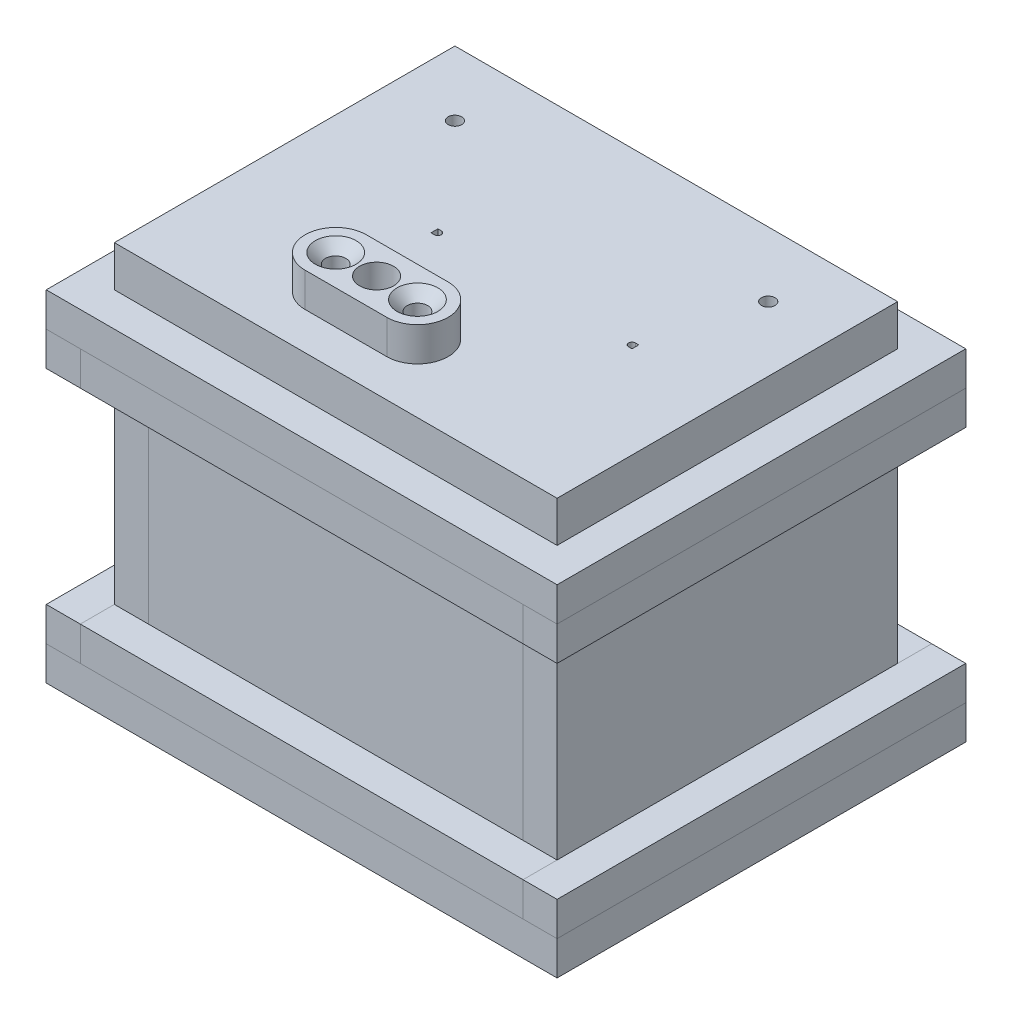
SolidWorks part; units mm, degrees
note: '?' marks a value the reader was unsure of. The reader was unsure of these and kept them because the rebuilt part matched: shared geometry of "Sketch2<6>", "Sketch41<4>", "Sketch41<3>".
ref_plane "Front Plane" through (0, 0, 0) normal (0, 0, 1) x (1, 0, 0)
ref_plane "Top Plane" through (0, 0, 0) normal (0, 1, 0) x (1, 0, 0)
ref_plane "Right Plane" through (0, 0, 0) normal (1, 0, 0) x (0, 0, -1)
sketch "Sketch1" plane through (0, 0, 0) normal (0, 1, 0) x (1, 0, 0)
  line L1 (-36, 0) -> (29, 0)
  line L2 (-36, 0) -> (-36, 50)
  line L3 (-36, 50) -> (29, 50)
  line L4 (29, 0) -> (29, 50)
  dimension "D1" = 50
  dimension "D2" = 36
  dimension "D3" = 29
extrude "Boss-Extrude1" add sketch "Sketch1" along normal blind 5 contours L2 L3 L4 L1
sketch "Sketch2" plane through (0, 5, 0) normal (0, 1, 0) x (1, 0, 0)
  line L0 (-36, 0) -> (29, 0) construction
  line L1 (-36, 50) -> (-31, 50)
  line L2 (-36, 50) -> (-36, 0)
  line L3 (-36, 0) -> (-31, 0)
  line L4 (-31, 50) -> (-31, 0)
  line L6 (29, 50) -> (24, 50)
  line L7 (29, 50) -> (29, 0)
  line L8 (29, 0) -> (24, 0)
  line L9 (24, 50) -> (24, 0)
  line L10 (-31, 50) -> (24, 50)
  line L11 (-31, 50) -> (-31, 45)
  line L12 (-31, 45) -> (24, 45)
  line L13 (24, 50) -> (24, 45)
  line L14 (-31, 0) -> (24, 0)
  line L15 (-31, 0) -> (-31, 5)
  line L16 (-31, 5) -> (24, 5)
  line L17 (24, 0) -> (24, 5)
  point P18 (24, 47.5)
  line M14 (-36, 0) -> (29, 0)
  line M15 (29, 0) -> (29, 50)
  line M16 (29, 50) -> (-36, 50)
  line M17 (-36, 50) -> (-36, 0)
  dimension "D1" = 5
extrude "Boss-Extrude24" add sketch "Sketch2" along normal blind 40 separate body contours L9 M16 M14 M15 | L4 M16 M17 M14 | L14 L17 L16 L15
extrude "Boss-Extrude25" add sketch "Sketch2<6>" along normal up to surface (40 mm away) separate body contours L4 L12 L9 M16 | L16 L4 L9 M14 up to face at (26.5, 45, -25)
sketch "Sketch2<6>" plane through (0, 5, 0) normal (0, 1, 0) x (1, 0, 0) same geometry as "Sketch2"
sketch "Sketch3" plane through (0, 45, 0) normal (0, 1, 0) x (1, 0, 0)
  line L1 (-36, 50) -> (29, 50)
  line L2 (-36, 50) -> (-36, 0)
  line L3 (-36, 0) -> (29, 0)
  line L4 (29, 50) -> (29, 0)
extrude "Boss-Extrude4" add sketch "Sketch3" along normal blind 5 separate body
sketch "Sketch18" plane through (0, 50, 0) normal (0, 1, 0) x (1, 0, 0)
  line L0 (-36, 0) -> (29, 0) construction
  line L1 (-28.5, 42.5) -> (21.5, 42.5)
  line L2 (-28.5, 42.5) -> (-28.5, 7.5)
  line L3 (-28.5, 7.5) -> (21.5, 7.5)
  line L8 (21.5, 42.5) -> (21.5, 7.5)
  line L12 (-31, 45) -> (24, 45) construction
  line L13 (-31, 50) -> (-31, 45) construction
  line L17 (24, 50) -> (24, 0) construction
  dimension "D1" = 2.5
  dimension "D2" = 2.5
  dimension "D3" = 7.5
  dimension "D8" = 2.5
extrude "Cut-Extrude3" cut sketch "Sketch18" against normal through all
sketch "Sketch17" plane through (0, 50, 0) normal (0, 1, 0) x (1, 0, 0)
  line L4 (-36, 50) -> (-36, 0)
  line L5 (-36, 0) -> (29, 0)
  line L6 (29, 0) -> (29, 50)
  line L7 (29, 50) -> (-36, 50)
  line L8 (-36, 50) -> (-36, 0)
  line L9 (-36, 0) -> (29, 0)
  line L10 (29, 0) -> (29, 50)
  line L11 (29, 50) -> (-36, 50)
  dimension "D1" = 0
extrude "Boss-Extrude8" add sketch "Sketch17" along normal blind 6 separate body
ref_plane "Anode" through (-14, 0, 0) normal (1, 0, 0) x (0, 0, -1)
sketch "Sketch6" plane through (-14, 0, 0) normal (1, 0, 0) x (0, 0, -1)
  line L0 (5, 25) -> (45, 25) construction
  line L2 (15.75, 45) -> (15.75, 15.75)
  line L3 (15.75, 15.75) -> (34.25, 15.75)
  line L4 (34.25, 45) -> (34.25, 15.75)
  line L5 (50, 45) -> (0, 45) construction
  line L6 (25, 18.75) -> (25, 31.25) construction
  line L7 (18.75, 31.25) -> (31.25, 31.25)
  line L8 (18.75, 31.25) -> (18.75, 18.75)
  line L9 (18.75, 18.75) -> (31.25, 18.75)
  line L10 (31.25, 31.25) -> (31.25, 18.75)
  line L12 (45, 45) -> (45, 5) construction
  line L16 (34.25, 45) -> (15.75, 45)
  line L17 (5, 45) -> (5, 5) construction
  line L22 (50, 50) -> (0, 50) construction
  line L23 (34.25, 45) -> (15.75, 45)
  line L24 (34.25, 45) -> (34.25, 50)
  line L25 (34.25, 50) -> (15.75, 50)
  line L26 (15.75, 45) -> (15.75, 50)
  point P15 (25, 25)
  dimension "D1" = 12.5
  dimension "D2" = 3
  dimension "D3" = 3
  dimension "D4" = 3
extrude "Boss-Extrude6" add sketch "Sketch6" along normal blind 5 separate body contours L26 L16 L24 L25
ref_plane "Cathode" through (10.5, 0, 0) normal (1, 0, 0) x (0, 0, -1)
sketch "Sketch7" plane through (10.5, 0, 0) normal (1, 0, 0) x (0, 0, -1)
  line L1 (15.75, 50) -> (34.25, 50)
  line L2 (15.75, 50) -> (15.75, 15.75)
  line L3 (15.75, 15.75) -> (34.25, 15.75)
  line L4 (34.25, 50) -> (34.25, 15.75)
extrude "Boss-Extrude7" add sketch "Sketch7" along normal blind 5 separate body
hole_wizard "M3 Clearance Hole1" [suppressed] positions "Sketch12" profile "Sketch10" hole size "M3" standard "ANSI Metric"
sketch "Sketch12" plane through (0, 56, 0) normal (0, 1, 0) x (1, 0, 0)
  line L1 (-36, 50) -> (-36, 0) construction
  line L9 (-31, 47.5) -> (-36, 47.5) construction
  line L16 (24, 47.5) -> (29, 47.5) construction
  line L18 (29, 0) -> (29, 50) construction
  line L19 (24, 25) -> (29, 25) construction
  line L21 (-36, 25) -> (-31, 25) construction
  line L23 (24, 2.5) -> (29, 2.5) construction
  line L26 (-31, 2.5) -> (-36, 2.5) construction
  line L54 (-13.5, 47.5) -> (-33.5, 47.5) construction
  line L66 (24, 50) -> (24, 45) construction
  line L67 (-31, 50) -> (-31, 45) construction
  line L68 (24, 50) -> (24, 0) construction
  line L69 (-31, 50) -> (-31, 0) construction
  line L70 (-13.5, 47.5) -> (6.5, 47.5) construction
  line L71 (6.5, 47.5) -> (26.5, 47.5) construction
  line L73 (6.5, 2.5) -> (26.5, 2.5) construction
  line L74 (-13.5, 2.5) -> (6.5, 2.5) construction
  line L75 (-13.5, 2.5) -> (-33.5, 2.5) construction
  point P47 (-33.5, 47.5)
  point P49 (-33.5, 25)
  point P55 (26.5, 47.5)
  point P57 (26.5, 25)
  point P68 (26.5, 2.5)
  point P71 (-33.5, 2.5)
  point P206 (-13.5, 47.5)
  point P209 (6.5, 47.5)
  point P212 (6.5, 47.5)
  point P218 (6.5, 2.5)
  point P219 (6.5, 2.5)
  point P220 (-13.5, 2.5)
sketch "Sketch10" plane through (-13.5, 56, -2.5) normal (1, 0, 0) x (0, 0, 1)
  line L0 (0, 0) -> (0, 56)
  line L1 (0, 56) -> (1.7, 56)
  line L2 (1.7, 56) -> (1.7, 0)
  line L5 (1.7, 0) -> (0, 0)
  line L11 (0, -6.35) -> (0, 107.95) construction
  dimension "Thru Hole Dia." = 3.4
  dimension "Thru Hole Depth" = 56
hole_wizard "M3x0.5 Tapped Hole1" [suppressed] positions "Sketch14" profile "Sketch15" tap size "M3x0.5" standard "ANSI Metric"
sketch "Sketch14" [suppressed] plane through (0, 50, 0) normal (0, 1, 0) x (1, 0, 0)
  point P0 (-33.5, 47.5)
  point P5 (6.5, 47.5)
  point P8 (26.5, 47.5)
  point P11 (26.5, 25)
  point P14 (26.5, 2.5)
  point P20 (6.5, 2.5)
  point P23 (-33.5, 2.5)
  point P26 (-33.5, 25)
  point P39 (-13.5, 2.5)
  point P42 (-13.5, 47.5)
sketch "Sketch15" plane through (-33.5, 50, -47.5) normal (1, 0, 0) x (0, 0, 1)
  line L0 (0, 0) -> (0, 8.2511)
  line L1 (0, 8.2511) -> (1.25, 7.5)
  line L2 (1.25, 7.5) -> (1.25, 0)
  line L5 (1.25, 0) -> (0, 0)
  line L10 (0, 8.2511) -> (-1.25, 7.5) construction
  line L11 (0, -6.35) -> (0, 107.95) construction
  dimension "Tap Drill Dia." = 2.5
  dimension "Tap Drill Depth" = 7.5
  dimension "Drill Angle" = 118
sketch "Sketch19" plane through (0, 56, 0) normal (0, 1, 0) x (1, 0, 0)
  line L0 (0.75, 25) -> (-13.5, 25) construction
  line L1 (21.5, 7.5) -> (21.5, 42.5) construction
  line L2 (-28.5, 42.5) -> (-28.5, 7.5) construction
  line L3 (-13.5, 25.5) -> (-14, 25.5)
  line L5 (-14, 25.5) -> (-14, 24.5)
  line L6 (-14, 24.5) -> (-13.5, 24.5)
  line L8 (21.5, 42.5) -> (-28.5, 42.5) construction
  line L14 (15, 25) -> (0.75, 25) construction
  line L15 (15.5, 34.25) -> (15.5, 15.75) construction
  line L16 (-26.5, 40.5) -> (19.5, 40.5) construction
  line L17 (-14, 25.5) -> (-13.5, 25.5)
  line L18 (15, 25) -> (15.5, 25) construction
  line L19 (19.5, 40.5) -> (19.5, 42.5) construction
  line L21 (-13.5, 24.5) -> (-14, 24.5)
  line L22 (-13.5, 25.5) -> (-14, 25.5)
  line L23 (-14, 24.5) -> (-13.5, 24.5)
  line L24 (-14, 25.5) -> (-13.5, 25.5)
  line L25 (-28.5, 7.5) -> (21.5, 7.5) construction
  line L26 (-13.5, 24.5) -> (-14, 24.5)
  line L27 (15, 24.5) -> (15.5, 24.5)
  line L28 (15.5, 25.5) -> (15, 25.5)
  line L31 (15.5, 24.5) -> (15, 24.5)
  line L32 (15, 25.5) -> (15.5, 25.5)
  line L33 (15, 24.5) -> (15.5, 24.5)
  line L34 (15.5, 25.5) -> (15, 25.5)
  line L35 (15.5, 24.5) -> (15, 24.5)
  line L36 (15.5, 25.5) -> (15.5, 24.5)
  line L37 (15, 25.5) -> (15.5, 25.5)
  line L39 (-14, 34.25) -> (-14, 15.75) construction
  arc A0 (-13.5, 24.5) -> (-13.5, 25.5) centre (-13.5, 25) ccw
  circle A2 centre (-7.5, 10) radius 2.5
  circle A3 centre (-26.5, 40.5) radius 1
  circle A4 centre (19.5, 40.5) radius 1
  arc A5 (15, 24.5) -> (15, 25.5) centre (15, 25) cw
  dimension "D1" = 1
  dimension "D2" = 5
  dimension "D5" = 2
  dimension "D7" = 2
  dimension "D8" = 2
  dimension "D3" = 2.5
  dimension "D4" = 21
  dimension "D6" = 2
extrude "Cut-Extrude4" cut sketch "Sketch19" against normal offset from surface (30.25 mm away) 10 contours A3 | L6 A0 L3 L5 | A2 | A4 | A5 L27 L36 L28 up to face at (-11.5, 15.75, -25)
sketch "Sketch23" [suppressed] plane through (0, 0, 0) normal (0, 0, 1) x (1, 0, 0)
  line L0 (-14, 50) -> (-14, 15.75) construction
  line L1 (-31, 42) -> (3, 42) construction
  line L2 (3, 25) -> (-31, 25) construction
  line L4 (-31, 45) -> (-31, 5) construction
  line L5 (3, 42) -> (3, 8) construction
  line L6 (-14, 39) -> (-14, 11) construction
  line L7 (-28, 39) -> (0, 39) construction
  line L8 (-28, 39) -> (-28, 11) construction
  line L9 (-28, 11) -> (0, 11) construction
  line L10 (0, 39) -> (0, 11) construction
  line L11 (-31, 8) -> (3, 8) construction
  line L12 (-31, 42) -> (-31, 8) construction
  circle A0 centre (-14, 25) radius 10
  circle A1 centre (-28, 39) radius 1.25
  circle A2 centre (0, 39) radius 1.25
  circle A3 centre (0, 11) radius 1.25
  circle A4 centre (-28, 11) radius 1.25
  circle A5 centre (-31, 42) radius 1.25
  circle A6 centre (3, 42) radius 1.25
  circle A7 centre (3, 8) radius 1.25
  circle A8 centre (-31, 8) radius 1.25
  point P12 (-14, 25)
  dimension "D1" = 20
  dimension "D3" = 2.5
  dimension "D2" = 28
  dimension "D4" = 3
sketch "Sketch24" [suppressed] plane through (-36, 0, -41) normal (1, 0, 0) x (0, 0, -1)
  line L0 (-33, 42) -> (1, 42) construction
  line L1 (-36, 45) -> (-36, 5) construction
  line L2 (4, 25) -> (-36, 25) construction
  line L3 (1, 42) -> (1, 8) construction
  line L4 (-33, 8) -> (1, 8) construction
  line L5 (4, 45) -> (4, 5) construction
  line L6 (-16, 39) -> (-16, 11) construction
  line L7 (-30, 39) -> (-2, 39) construction
  line L8 (-30, 39) -> (-30, 11) construction
  line L9 (-30, 11) -> (-2, 11) construction
  line L10 (-2, 39) -> (-2, 11) construction
  line L11 (-33, 42) -> (-33, 8) construction
  circle A0 centre (-16, 25) radius 10
  circle A1 centre (-30, 39) radius 1.25
  circle A2 centre (-2, 39) radius 1.25
  circle A3 centre (-2, 11) radius 1.25
  circle A4 centre (-30, 11) radius 1.25
  circle A5 centre (1, 42) radius 1.25
  circle A6 centre (-33, 42) radius 1.25
  circle A7 centre (-33, 8) radius 1.25
  circle A8 centre (1, 8) radius 1.25
  point P12 (-16, 25)
  point P23 (-16, 25)
  dimension "D1" = 20
  dimension "D3" = 2.5
  dimension "D2" = 28
  dimension "D4" = 3
ref_plane "Plane1" through (0, 25, 0) normal (0, -1, 0) x (-1, 0, 0)
ref_plane "Plane2" through (0, 0, -25) normal (0, 0, 1) x (1, 0, 0)
ref_plane "Plane3" through (-14, 0, 0) normal (-1, 0, 0) x (0, 0, 1)
ref_axis "Axis1" through (47.9997, 25, -25) along (-1, 0, 0)?
ref_axis "Axis2" through (-14, 25, 7.75) along (0, 0, -1)?
ref_plane "Plane4" through (0, 0, 41.5) normal (0, 0, 1) x (1, 0, 0)
sketch "Sketch31" plane through (0, 56, 0) normal (0, 1, 0) x (1, 0, 0)
  line L0 (-10, 10) -> (-13.5, 10) construction
  line L2 (-7.5, 7.5) -> (-7.5, 12.5) construction
  line L3 (-1.5, 10) -> (-13.5, 10) construction
  line L4 (-1.5, 5.5) -> (-13.5, 5.5)
  line L5 (-1.5, 14.5) -> (-13.5, 14.5)
  circle A1 centre (-7.5, 10) radius 2.5
  circle A2 centre (-7.5, 10) radius 2.5 construction
  circle A3 centre (-13.5, 10) radius 1.5
  circle A4 centre (-1.5, 10) radius 1.5
  arc A5 (-1.5, 5.5) -> (-1.5, 14.5) centre (-1.5, 10) ccw
  arc A6 (-13.5, 14.5) -> (-13.5, 5.5) centre (-13.5, 10) ccw
  point P14 (-7.5, 10)
  dimension "D1" = 9
  dimension "D2" = 3
  dimension "D3" = 12
extrude "Boss-Extrude18" add sketch "Sketch31" along normal blind 5 separate body
chamfer "Chamfer1" distance 2 angle 45 1 edges at (-7.5, 56, -7.5)
chamfer "Chamfer2" distance 1.5 angle 45 2 edges at (-1.5, 61, -11.5) (-13.5, 61, -8.5)
hole_wizard "M3x0.5 Tapped Hole2" [suppressed] positions "Sketch32" profile "Sketch34" tap size "M3x0.5" standard "ANSI Metric"
sketch "Sketch32" plane through (0, 56, 0) normal (0, 1, 0) x (1, 0, 0)
  point P0 (-13.5, 10)
  point P3 (-1.5, 10)
sketch "Sketch34" plane through (-13.5, 56, -10) normal (1, 0, 0) x (0, 0, 1)
  line L0 (0, 0) -> (0, 56)
  line L1 (0, 56) -> (1.25, 56)
  line L2 (1.25, 56) -> (1.25, 0)
  line L5 (1.25, 0) -> (0, 0)
  line L11 (0, -6.35) -> (0, 107.95) construction
  dimension "Thru Tap Drill Dia." = 2.5
  dimension "Thru Tap Drill Depth" = 56
hole_wizard "CSK for M3 Flat Head Machine Screw1" [suppressed] positions "Sketch35" profile "Sketch36" countersink size "M3" standard "ANSI Metric"
sketch "Sketch35" plane through (0, 56, 0) normal (0, 1, 0) x (1, 0, 0)
  line L0 (15, 25) -> (10.5, 25) construction
  line L3 (13, 19.75) -> (13, 25) construction
  line L4 (10.5, 34.25) -> (10.5, 15.75) construction
  line L5 (15.5, 24.5) -> (15.5, 15.75) construction
  line L6 (15.5, 15.75) -> (10.5, 15.75) construction
  line L7 (0.75, 7.5) -> (0.75, 42.5) construction
  line L9 (21.5, 42.5) -> (-28.5, 42.5) construction
  line L10 (-28.5, 7.5) -> (21.5, 7.5) construction
  line L11 (-9, 34.25) -> (-9, 15.75) construction
  point P0 (13, 19.75)
  point P32 (13, 30.25)
  point P39 (-11.5, 30.25)
  point P40 (-11.5, 19.75)
  dimension "D1" = 4
sketch "Sketch36" plane through (13, 56, -19.75) normal (1, 0, 0) x (0, 0, 1)
  line L0 (0, 0) -> (0, 56)
  line L1 (0, 56) -> (1.7, 56)
  line L2 (1.7, 56) -> (1.7, 1.45)
  line L3 (1.7, 1.45) -> (3.15, 0)
  line L5 (3.15, 0) -> (0, 0)
  line L6 (-1.7, 1.45) -> (-3.15, 0) construction
  line L11 (0, -6.35) -> (0, 107.95) construction
  dimension "Thru Hole Dia." = 3.4
  dimension "Thru Hole Depth" = 56
  dimension "Near C'Sink Dia." = 6.3
  dimension "Near C'Sink Angle" = 90
hole_wizard "M3x0.5 Tapped Hole3" [suppressed] positions "Sketch37" profile "Sketch38" tap size "M3x0.5" standard "ANSI Metric"
sketch "Sketch37" [suppressed] plane through (0, 50, 0) normal (0, 1, 0) x (1, 0, 0)
  point P0 (13, 30.25)
  point P3 (13, 19.75)
  point P6 (-11.5, 30.25)
  point P9 (-11.5, 19.75)
sketch "Sketch38" plane through (13, 50, -30.25) normal (1, 0, 0) x (0, 0, 1)
  line L0 (0, 0) -> (0, 9.2511)
  line L1 (0, 9.2511) -> (1.25, 8.5)
  line L2 (1.25, 8.5) -> (1.25, 0)
  line L5 (1.25, 0) -> (0, 0)
  line L10 (0, 9.2511) -> (-1.25, 8.5) construction
  line L11 (0, -6.35) -> (0, 107.95) construction
  dimension "Tap Drill Dia." = 2.5
  dimension "Tap Drill Depth" = 8.5
  dimension "Drill Angle" = 118
cosmetic thread "Hole Thread15" [suppressed] parameters "D1"=6, "D2"=3
cosmetic thread "Hole Thread16" [suppressed] parameters "D1"=6, "D2"=3
cosmetic thread "Hole Thread17" [suppressed] parameters "D1"=6, "D2"=3
cosmetic thread "Hole Thread18" [suppressed] parameters "D1"=6, "D2"=3
sketch "Sketch42" plane through (0, 50, 0) normal (0, 1, 0) x (1, 0, 0)
  line L0 (34, -5) -> (34, 55)
  line L1 (34, 55) -> (-41, 55)
  line L2 (-41, 55) -> (-41, -5)
  line L3 (-41, -5) -> (34, -5)
  line L4 (-36, 50) -> (-36, 0)
  line L5 (-36, 0) -> (29, 0)
  line L6 (29, 0) -> (29, 50)
  line L7 (29, 50) -> (-36, 50)
  line L8 (-36, 50) -> (-36, 0)
  line L9 (-36, 0) -> (29, 0)
  line L10 (29, 0) -> (29, 50)
  line L11 (29, 50) -> (-36, 50)
  line M21 (-36, 50) -> (-36, 0)
  line M22 (-36, 0) -> (29, 0)
  line M23 (29, 0) -> (29, 50)
  line M24 (29, 50) -> (-36, 50)
  dimension "D1" = 0
  dimension "D2" = 5
extrude "Boss-Extrude22" add sketch "Sketch42" against normal up to surface (5 mm away) contours L2 L3 L0 L1 M21 M24 M23 M22 up to face at (-3.5, 45, -25)
sketch "Sketch41" plane through (0, 5, 0) normal (0, 1, 0) x (1, 0, 0)
  line L4 (-36, 0) -> (29, 0)
  line L5 (29, 0) -> (29, 50)
  line L6 (29, 50) -> (-36, 50)
  line L7 (-36, 50) -> (-36, 0)
  line L8 (-36, 0) -> (29, 0)
  line L9 (29, 0) -> (29, 50)
  line L10 (29, 50) -> (-36, 50)
  line L11 (-36, 50) -> (-36, 0)
  line L12 (-36, 50) -> (-36, 55)
  line L13 (-36, 0) -> (-36, -5)
  line L14 (29, 0) -> (29, -5)
  line L15 (29, 50) -> (29, 55)
  line L16 (-41, -5) -> (34, -5)
  line L17 (34, -5) -> (34, 55)
  line L18 (34, 55) -> (-41, 55)
  line L19 (-41, 55) -> (-41, -5)
  line L20 (-41, -5) -> (34, -5)
  line L21 (34, -5) -> (34, 55)
  line L22 (34, 55) -> (-41, 55)
  line L23 (-41, 55) -> (-41, -5)
  line M9 (-36, 0) -> (29, 0)
  line M10 (29, 0) -> (29, 50)
  line M11 (29, 50) -> (-36, 50)
  line M12 (-36, 50) -> (-36, 0)
  dimension "D1" = 0
  dimension "D2" = 5
extrude "Boss-Extrude23" add sketch "Sketch41<4>" along direction (0, -1, 0) on the side against the normal up to surface (5 mm away) contours L22 L23 L20 L21 up to face at (-3.5, 0, -25)
sketch "Sketch41<4>" plane through (0, 5, 0) normal (0, 1, 0) x (1, 0, 0) same geometry as "Sketch41"
extrude "Boss-Extrude20" add sketch "Sketch41" along normal blind 5 separate body contours L22 L23 L20 L13 L12 M12 | L21 L22 L15 L14 L20 M10
extrude "Boss-Extrude21" add sketch "Sketch41<3>" along normal blind 5 separate body contours L15 L22 L12 M11 | L13 L20 L14 M9
sketch "Sketch41<3>" plane through (0, 5, 0) normal (0, 1, 0) x (1, 0, 0) same geometry as "Sketch41"
mirror "Mirror1" about plane through (0, 25, 0) normal (0, -1, 0) of bodies 176 175 174 177
equation "\"t\"= 5"
equation "\"D1@Boss-Extrude1\"=\"t\""
equation "\"D1@Sketch2\"=\"t\""
equation "\"D1@Boss-Extrude4\"=\"t\""
equation "\"D1@Sketch1\"=40mm+2*\"t\""
equation "\"D2@Sketch1\"=28mm+3mm+\"t\""
equation "\"D3@Sketch1\"=21mm+3mm+\"t\""
